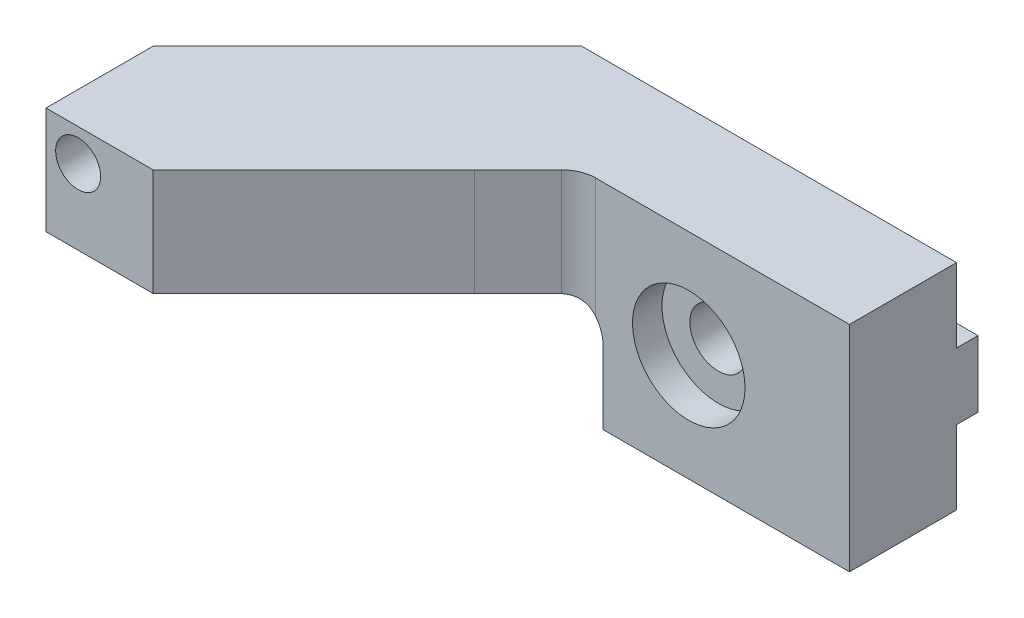
SolidWorks part; units mm, degrees
ref_plane "Front Plane" through (0, 0, 0) normal (0, 0, 1) x (1, 0, 0)
ref_plane "Top Plane" through (0, 0, 0) normal (0, 1, 0) x (1, 0, 0)
ref_plane "Right Plane" through (0, 0, 0) normal (1, 0, 0) x (0, 0, -1)
sketch "Sketch1" plane through (0, 0, 0) normal (0, 0, 1) x (1, 0, 0)
  line L1 (0, 0) -> (15, 0)
  line L2 (0, 0) -> (0, 20)
  line L3 (0, 20) -> (15, 20)
  line L4 (15, 0) -> (15, 20)
  point P5 (8, 17)
  dimension "D1" = 20
  dimension "D2" = 15
  dimension "D3" = 3
  dimension "D4" = 8
extrude "Boss-Extrude1" add sketch "Sketch1" along normal blind 10
sketch "Sketch2" plane through (0, 0, 10) normal (0, 0, 1) x (1, 0, 0)
  point P0 (8, 17)
hole_wizard "Ø4.2 (4.2) Diameter Hole1" positions "Sketch2" profile "Sketch3" hole size "Ø4.2" standard "ANSI Metric" end condition through all
sketch "Sketch3" plane through (8, 17, 10) normal (1, 0, 0) x (0, -1, 0)
  line L0 (0, 0) -> (0, 10)
  line L1 (0, 10) -> (2.1, 10)
  line L2 (2.1, 10) -> (2.1, 0)
  line L5 (2.1, 0) -> (0, 0)
  line L11 (0, -6.35) -> (0, 107.95) construction
  dimension "Thru Hole Dia." = 4.2
  dimension "Thru Hole Depth" = 10
sketch "Sketch4" plane through (15, 0, 0) normal (1, 0, 0) x (0, 0, -1)
  line L4 (0, 0) -> (0, 20)
  line L5 (0, 20) -> (-10, 20)
  line L6 (-10, 20) -> (-10, 0)
  line L7 (-10, 0) -> (0, 0)
  line L8 (0, 0) -> (0, 20)
  line L9 (0, 20) -> (-10, 20)
  line L10 (-10, 20) -> (-10, 0)
  line L11 (-10, 0) -> (0, 0)
  dimension "D1" = 0
extrude "Boss-Extrude2" add sketch "Sketch4" along normal blind 15
sketch "Sketch5" plane through (0, 0, 0) normal (0, 0, -1) x (-1, 0, 0)
  line L1 (-30, 20) -> (-15, 20)
  line L2 (-30, 20) -> (-30, 0)
  line L3 (-30, 0) -> (-15, 0)
  line L4 (-15, 20) -> (-15, 0)
  line L5 (-30, 20) -> (0, 20) construction
extrude "Boss-Extrude3" add sketch "Sketch5" along normal blind 20
chamfer "Chamfer1" distance 10 angle 45 1 edges at (15, 10, 0)
chamfer "Chamfer2" distance 15 angle 45 1 edges at (30, 10, 10)
sketch "Sketch6" plane through (0, 0, 0) normal (0, 0, -1) x (-1, 0, 0)
  line L4 (0, 20) -> (-5, 20)
  line L5 (-5, 20) -> (-5, 0)
  line L6 (-5, 0) -> (0, 0)
  line L7 (0, 0) -> (0, 20)
  line L8 (0, 20) -> (-5, 20)
  line L9 (-5, 20) -> (-5, 0)
  line L10 (-5, 0) -> (0, 0)
  line L11 (0, 0) -> (0, 20)
  dimension "D1" = 0
extrude "Cut-Extrude1" cut sketch "Sketch6" against normal blind 10
sketch "Sketch7" plane through (30, 0, 0) normal (1, 0, 0) x (0, 0, -1)
  line L0 (5, 0) -> (20, 0) construction
  line L1 (20, 20) -> (10, 20)
  line L2 (20, 20) -> (20, 0)
  line L3 (20, 0) -> (10, 0)
  line L4 (10, 20) -> (10, 0)
  dimension "D1" = 10
sketch "Sketch8" plane through (30, 0, 0) normal (1, 0, 0) x (0, 0, -1)
  line L0 (5, 20) -> (5, 0) construction
  line L1 (20, 20) -> (5, 20)
  line L2 (20, 20) -> (20, 0)
  line L3 (20, 0) -> (5, 0)
  line L4 (5, 20) -> (5, 0)
extrude "Boss-Extrude4" add sketch "Sketch8" along normal blind 10
chamfer "Chamfer3" distance 10 angle 45 1 edges at (40, 10, -5)
extrude "Boss-Extrude5" add sketch "Sketch7" along normal blind 25
fillet "Fillet5" radius 3.175 1 edges at (35, 10, -10)
sketch "Sketch9" plane through (0, 0, -20) normal (0, 0, -1) x (-1, 0, 0)
  line L0 (-15, 0) -> (-15, 20) construction
  line L1 (-5, 0) -> (-15, 0)
  line L2 (-5, 0) -> (-5, 10)
  line L3 (-5, 10) -> (-15, 10)
  line L4 (-15, 0) -> (-15, 10)
  dimension "D1" = 10
extrude "Cut-Extrude4" cut sketch "Sketch9" against normal blind 37
sketch "Sketch12" plane through (0, 0, 10) normal (0, 0, 1) x (1, 0, 0)
  line L0 (30, 0) -> (15, 0) construction
  line L1 (55, 20) -> (35, 20) construction
  line L2 (55, 20) -> (55, 0) construction
  line L3 (55, 0) -> (35, 0) construction
  line L4 (35, 20) -> (35, 0) construction
  line L5 (35, 20) -> (15, 20) construction
  line L6 (35, 20) -> (35, 0) construction
  line L7 (35, 0) -> (15, 0) construction
  line L8 (15, 20) -> (15, 0) construction
  line L9 (25, 10) -> (45, 10) construction
  point P11 (45, 10)
  point P12 (25, 10)
  point P13 (35, 10)
  dimension "D1" = 20
  dimension "D2" = 20
hole_wizard "CBORE for M5 SBHCS2" positions "Sketch12" profile "Sketch14" counterbore size "M5" standard "ANSI Metric"
sketch "Sketch14" plane through (45, 10, 10) normal (1, 0, 0) x (0, -1, 0)
  line L0 (0, 0) -> (0, 30)
  line L1 (0, 30) -> (2.65, 30)
  line L3 (2.65, 30) -> (2.65, 22.75)
  line L4 (5.25, 22.75) -> (2.65, 22.75)
  line L5 (5.25, 22.75) -> (5.25, 0.021)
  line L6 (5.25, 0.021) -> (5.275, 0)
  line L7 (5.275, 0) -> (0, 0)
  line L8 (-5.25, 0.021) -> (-5.275, 0) construction
  line L11 (0, -6.35) -> (0, 107.95) construction
  dimension "Thru Hole Dia." = 5.3
  dimension "Thru Hole Depth" = 30
  dimension "C'Bore Dia." = 10.5
  dimension "C'Bore Depth" = 22.75
  dimension "Near C'Sink Dia." = 10.55
  dimension "Near C'Sink Angle" = 100
sketch "Sketch15" plane through (2.5, 0, 2.5) normal (-0.7071, 0, -0.7071) x (-0.7071, 0, 0.7071)
  line L1 (-32.3287, 27.0207) -> (2.959, 27.0207)
  line L2 (-32.3287, 27.0207) -> (-32.3287, -8.2499)
  line L3 (-32.3287, -8.2499) -> (2.959, -8.2499)
  line L4 (2.959, 27.0207) -> (2.959, -8.2499)
extrude "Cut-Extrude5" cut sketch "Sketch15" along normal blind 10
sketch "Sketch16" plane through (0, 0, -20) normal (0, 0, -1) x (-1, 0, 0)
  line L1 (-5, 10) -> (-37, 10)
  line L2 (-5, 10) -> (-5, 0)
  line L3 (-5, 0) -> (-37, 0)
  line L4 (-37, 10) -> (-37, 0)
  line L6 (-55, 0) -> (-55, 20) construction
  dimension "D1" = 10
  dimension "D2" = 18
extrude "Cut-Extrude6" cut sketch "Sketch16" against normal blind 46
other "Move Face1" face at (55, 10, -15) parameters "D1"=5
sketch "Sketch19" plane through (0, 0, -20) normal (0, 0, -1) x (-1, 0, 0)
  line L0 (-60, 0) -> (-60, 20) construction
  line L1 (-60, 13.1) -> (-58, 13.1)
  line L2 (-60, 13.1) -> (-60, 6.9)
  line L3 (-60, 6.9) -> (-58, 6.9)
  line L4 (-58, 13.1) -> (-58, 6.9)
  point P6 (-60, 10)
  point P7 (-60, 10)
  dimension "D1" = 6.2
  dimension "D2" = 2
extrude "Boss-Extrude6" add sketch "Sketch19" along normal blind 2
fillet "Fillet6" radius 6.35 1 edges at (58, 10, -20)
fillet "Fillet7" radius 3.175 1 edges at (37, 10, -15)
